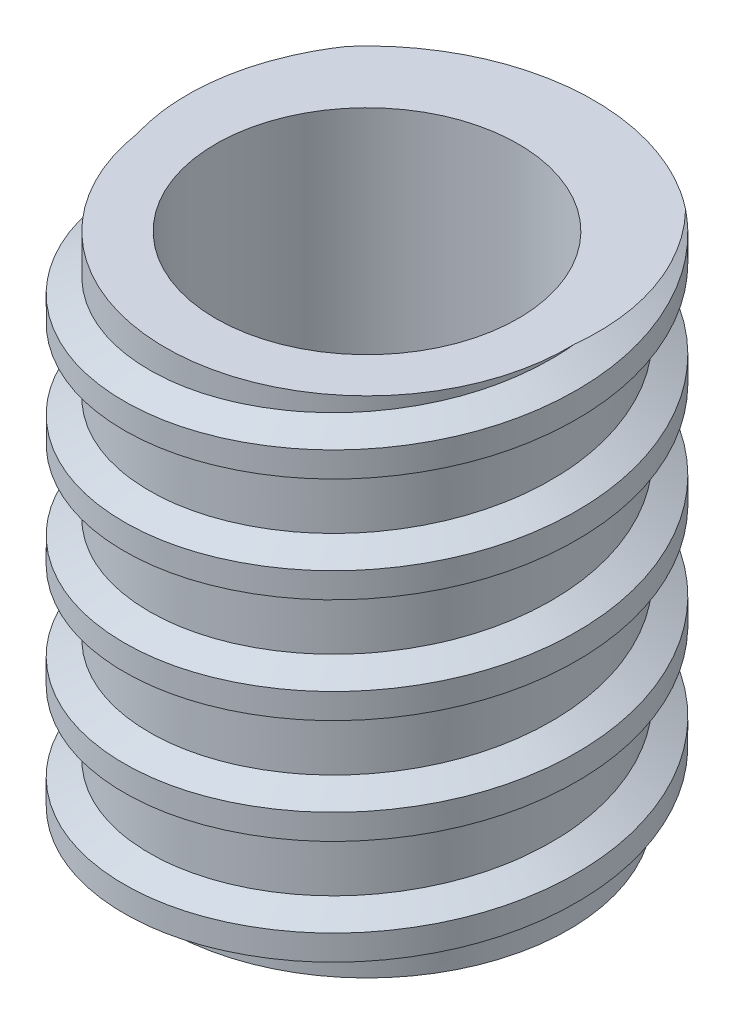
SolidWorks part; units mm, degrees
ref_plane "Front" through (0, 0, 0) normal (0, 0, 1) x (1, 0, 0)
ref_plane "Top" through (0, 0, 0) normal (0, 1, 0) x (1, 0, 0)
ref_plane "Right" through (0, 0, 0) normal (1, 0, 0) x (0, 0, -1)
sketch "Sketch1" plane through (0, 0, 0) normal (0, 1, 0) x (1, 0, 0)
  circle A1 centre (0, 0) radius 8
  circle A2 centre (0, 0) radius 6
  dimension "D1" = 12
  dimension "D2" = 2
extrude "Boss-Extrude1" add sketch "Sketch1" along normal blind 20
ref_plane "Plane1" through (0, -5, 0) normal (0, -1, 0) x (-1, 0, 0)
sketch "Sketch3" plane through (0, 0, 0) normal (0, 0, 1) x (1, 0, 0)
  line L0 (-9.3917, -5) -> (9.3917, -5) construction
  line L4 (-8, -5) -> (-8, -2.8453)
  line L6 (-8, -5) -> (-9, -4.4226)
  line L7 (-9, -4.4226) -> (-9, -3.4226)
  line L8 (-9, -3.4226) -> (-8, -2.8453)
  dimension "D1" = 60
  dimension "D2" = 60
  dimension "D3" = 1
  dimension "D4" = 1
sketch "Sketch6" plane through (0, 0, 0) normal (0, -1, 0) x (1, 0, 0)
  circle A0 centre (0, 0) radius 8
  circle A1 centre (0, 0) radius 8 construction
  dimension "D1" = 16
curve "Helix/Spiral1" pitch 4.15 height 40.4625 radius 8 centre (0, 0, 0) axis (0, 1, 0) start towards (0, 0, -1)
sweep "Sweep1" add profiles "Sketch3" path "Helix/Spiral1"
sketch "Sketch8" plane through (0, 20, 0) normal (0, 1, 0) x (1, 0, 0)
  circle A0 centre (0, 0) radius 17.3214
  circle A1 centre (0, 0) radius 8 construction
  dimension "D1" = 34.6429
extrude "Cut-Extrude1" cut sketch "Sketch8" along normal through all
sketch "Sketch9" plane through (0, 0, 0) normal (0, -1, 0) x (1, 0, 0)
  circle A0 centre (0, 0) radius 15.434
  dimension "D1" = 30.868
extrude "Cut-Extrude2" cut sketch "Sketch9" along normal through all
ref_axis "Axis1" through (0, 20, 0) along (0, -1, 0)
